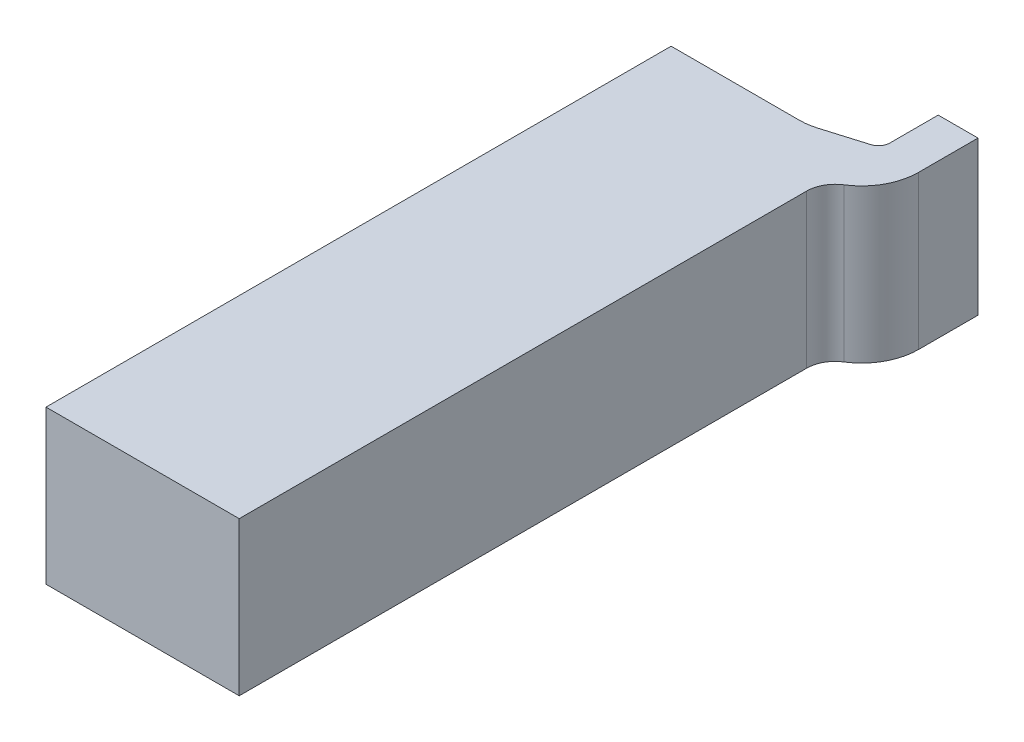
SolidWorks part; units mm, degrees
ref_plane "Спереди" through (0, 0, 0) normal (0, 0, 1) x (1, 0, 0)
ref_plane "Сверху" through (0, 0, 0) normal (0, 1, 0) x (1, 0, 0)
ref_plane "Справа" through (0, 0, 0) normal (1, 0, 0) x (0, 0, -1)
sketch "Эскиз1" plane through (0, 0, 0) normal (0, 1, 0) x (1, 0, 0)
  line L0 (0, 55) -> (0, -55) construction
  line L1 (-17, 55) -> (17, 55)
  line L2 (-17, 55) -> (-17, -55)
  line L3 (-17, -55) -> (17, -55)
  line L4 (17, 55) -> (17, -55)
  line L6 (-17, 0) -> (17, 0) construction
  point P6 (0, 0)
  dimension "D1" = 34
  dimension "D2" = 110
extrude "тело" add sketch "Эскиз1" along normal blind 13.5 and the other way blind 13.5
sketch "Эскиз2" plane through (17, 0, 0) normal (1, 0, 0) x (0, 0, -1)
  line L0 (-55, 13.5) -> (55, 13.5) construction
  line L1 (48, 13.5) -> (68, 13.5)
  line L2 (48, 13.5) -> (48, -13.5)
  line L3 (48, -13.5) -> (68, -13.5)
  line L4 (68, 13.5) -> (68, -13.5)
  line L5 (-55, -13.5) -> (55, -13.5) construction
  line L6 (55, -13.5) -> (55, 13.5) construction
  dimension "D1" = 7
  dimension "D2" = 13
extrude "выступ проводов" add sketch "Эскиз2" along normal blind 7
chamfer "Фаска1" distance 10 distance2 3 1 edges at (17, 0, -55) first distance on face at (0, 0, -55)
fillet "Скругление2" radius 10 2 edges at (7, 0, -55) (24, 0, -48)
fillet "Скругление3" radius 5 1 edges at (17, 0, -48)
fillet "Скругление4" radius 2 1 edges at (17, 0, -58)
